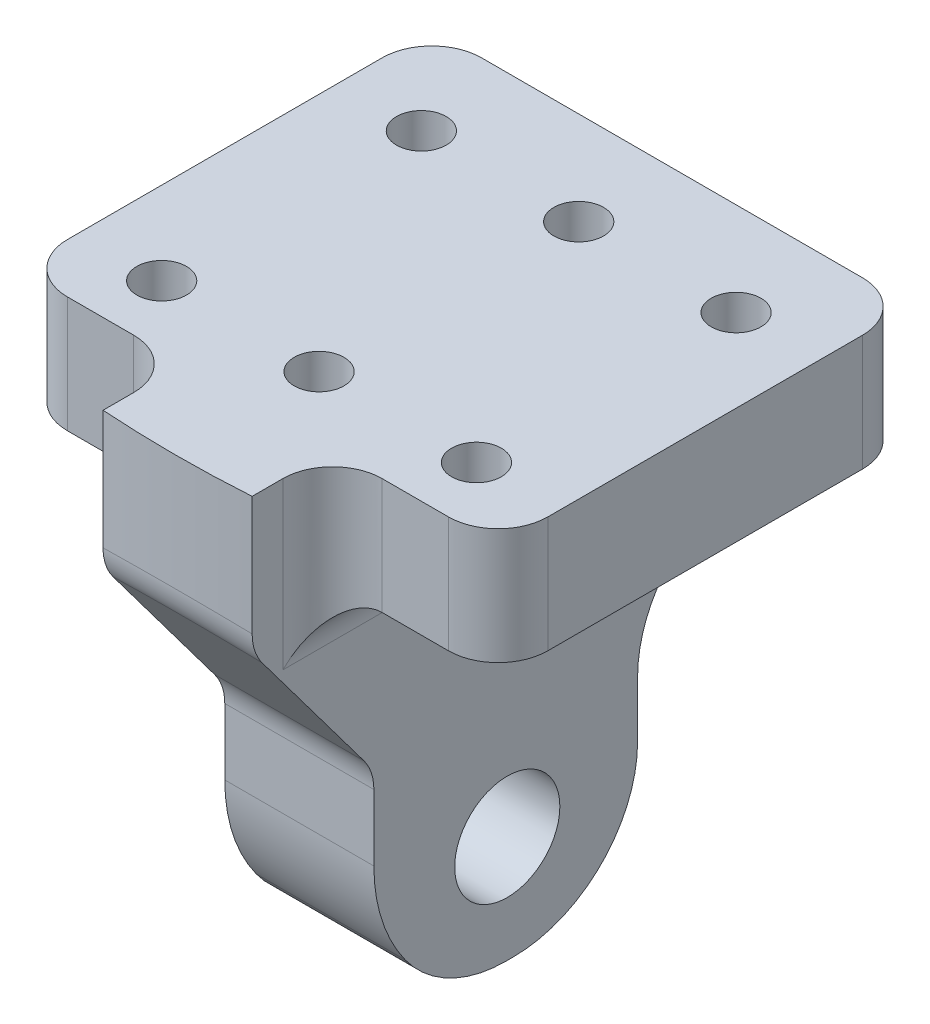
SolidWorks part; units mm, degrees
material "Custom Plastic"
ref_plane "Front Plane" through (0, 0, 0) normal (0, 0, 1) x (1, 0, 0)
ref_plane "Top Plane" through (0, 0, 0) normal (0, 1, 0) x (1, 0, 0)
ref_plane "Right Plane" through (0, 0, 0) normal (1, 0, 0) x (0, 0, -1)
sketch "Sketch1" plane through (0, 0, 0) normal (0, 1, 0) x (1, 0, 0)
  line L0 (0, 0) -> (0, 15.5524)
  line L2 (4.5, 0.1524) -> (4.5, 30)
  line L3 (4.5, 30) -> (-4.5, 30)
  line L4 (-4.5, 30) -> (-4.5, 0.1524)
  line L5 (0, 15.5524) -> (4.5, 15.5524)
  line L6 (0, 66.5) -> (0, 0) construction
  line L7 (-4.5, 0.1524) -> (4.5, 0.1524)
  circle A0 centre (0, 66.5) radius 66.5
  dimension "D3" = 133
  dimension "D1" = 9
  dimension "D2" = 30
  dimension "D4" = 15.4
extrude "Boss-Extrude1" add sketch "Sketch1" against normal blind 33 contours L0 L5 L2 L3 L4 | L5 L0 L2 | L7 A0 L0 | L0 A0 L7 | L7 L2 L3 L4 region at (-1.6878, 0, -0.0915) region at (1.6878, 0, -0.0915) region at (-0.7823, 0, -17.5877) region at (2.25, 0, -7.8524)
sketch "Sketch2" plane through (4.5, 0, 0) normal (1, 0, 0) x (0, 0, -1)
  line L0 (15.5524, 0) -> (15.5524, -33)
  line L1 (0.1524, -33) -> (30, -33) construction
  line L2 (15.5524, 0) -> (15.5524, -25.5)
  line L3 (0, 0) -> (0, -3)
  line L4 (0, 0) -> (0, -33) construction
  line L7 (0.1524, -33) -> (30, -33) construction
  line L8 (0, -3) -> (0, -33)
  line L9 (0, -33) -> (7.5, -33)
  line L10 (7.5, -33) -> (7.5, -18)
  line L15 (7.5, -18) -> (0, -18)
  line L16 (7.5, -18) -> (0, -8)
  circle A0 centre (15.5524, -25.5) radius 3.175
  line M4 (0.1524, -33) -> (30, -33)
  line M12 (0.1524, 0) -> (0.1524, -33)
  dimension "D2" = 6.35
  dimension "D1" = 7.5
  dimension "D3" = 15
  dimension "D4" = 7.5
  dimension "D5" = 10
extrude "Cut-Extrude1" cut sketch "Sketch2" against normal blind 20 contours L2 A0 L0 | L0 A0 L2 region at (4.5, -25.5, -16.8999) region at (4.5, -25.5, -14.2049)
extrude "Cut-Extrude2" cut sketch "Sketch2<4>" against normal blind 20 contours L10 L15 M12 M4 | L15 L8 L9 M12 | L15 L16 M12 | L16 L8 L15 M12 region at (4.5, -25.5, -3.8262) region at (4.5, -25.5, -0.0762) region at (4.5, -14.7344, -2.6016) region at (4.5, -13.0506, -0.076)
sketch "Sketch2<4>" plane through (4.5, 0, 0) normal (1, 0, 0) x (0, 0, -1) same geometry as "Sketch2"
fillet "Fillet1" radius 10 1 edges at (0, -33, -7.5)
sketch "Sketch3" plane through (0, 0, 0) normal (0, 1, 0) x (1, 0, 0)
  line L0 (4.5, 5.0023) -> (4.5, 12.3823)
  line L1 (-4.5, 30) -> (4.5, 30)
  line L2 (-4.5, 30) -> (-4.5, 5.0023)
  line L3 (-4.5, 5.0023) -> (4.5, 5.0023)
  line L4 (4.5, 30) -> (4.5, 5.0023)
  line L5 (4.5, 12.3823) -> (-4.5, 12.3823)
  line L6 (0, 18.7323) -> (0, 30)
  line L7 (-4.5, 12.3823) -> (4.5, 12.3823)
  line L8 (-4.5, 12.3823) -> (-4.5, 18.7323)
  line L9 (-4.5, 18.7323) -> (4.5, 18.7323)
  line L10 (4.5, 12.3823) -> (4.5, 18.7323)
  line L11 (0, 5.0023) -> (0, 12.3823)
  line L12 (0, 5.0023) -> (0, 8.6923)
  line L13 (0, 8.6923) -> (-4.5, 8.6923)
  line L14 (-4.5, 8.6923) -> (4.5, 8.6923)
  line L15 (-4.5, 5.0023) -> (-4.5, 0.1524)
  line L16 (-4.5, 0.1524) -> (4.5, 0.1524)
  line L17 (-9.5, 30) -> (-9.5, 5.0023) construction
  line L18 (4.5, 30) -> (14.5, 30)
  line L19 (4.5, 30) -> (4.5, 5.0023)
  line L20 (4.5, 5.0023) -> (14.5, 5.0023)
  line L21 (14.5, 30) -> (14.5, 5.0023)
  line L22 (-4.5, 5.0023) -> (-14.5, 5.0023)
  line L23 (-4.5, 5.0023) -> (-4.5, 30)
  line L24 (-4.5, 30) -> (-14.5, 30)
  line L25 (-14.5, 5.0023) -> (-14.5, 30)
  line L26 (9.5, 30) -> (9.5, 5.0023) construction
  line L27 (14.5, 24.3661) -> (-14.5, 24.3661) construction
  line L28 (14.5, 8.6923) -> (-14.5, 8.6923) construction
  circle A0 centre (0, 24.3661) radius 1.5
  circle A1 centre (0, 8.6923) radius 1.5
  circle A2 centre (-9.5, 24.3661) radius 1.5
  circle A3 centre (-9.5, 8.6923) radius 1.5
  circle A4 centre (9.5, 8.6923) radius 1.5
  circle A5 centre (9.5, 24.3661) radius 1.5
  point P13 (0, 24.3661)
  point P36 (0, 24.3661)
  point P39 (0, 8.6923)
  line M11 (-4.5, 30) -> (-4.5, 0.1524)
  line M13 (4.5, 0.1524) -> (4.5, 30)
  dimension "D3" = 3
  dimension "D1" = 12.2298
  dimension "D2" = 6.35
  dimension "D4" = 15.6739
  dimension "D5" = 3.69
  dimension "D6" = 4.5
  dimension "D7" = 10
extrude "Cut-Extrude3" cut sketch "Sketch3" against normal blind 7 contours A0
extrude "Cut-Extrude4" cut sketch "Sketch3<3>" against normal blind 7 contours A1
sketch "Sketch3<3>" plane through (0, 0, 0) normal (0, 1, 0) x (1, 0, 0) same geometry as "Sketch3"
extrude "Boss-Extrude2" add sketch "Sketch3<4>" against normal blind 10 contours L25 L22 L2 L24 A3 A2 M11 | L21 L18 L4 L20 A5 A4 M13 | A2 | A5 | A3 | A4 region at (9.5, 0, -17.5594) region at (-9.5, 0, -17.5594) region at (-9.5, 0, -24.3661) region at (-9.5, 0, -8.6923) region at (9.5, 0, -8.6923) region at (9.5, 0, -24.3661)
sketch "Sketch3<4>" plane through (0, 0, 0) normal (0, 1, 0) x (1, 0, 0) same geometry as "Sketch3"
extrude "Cut-Extrude5" cut sketch "Sketch3<5>" against normal blind 8 contours A3 | A4 | A5 | A2 region at (-9.5, 0, -8.6923) region at (9.5, 0, -8.6923) region at (9.5, 0, -24.3661)
sketch "Sketch3<5>" plane through (0, 0, 0) normal (0, 1, 0) x (1, 0, 0) same geometry as "Sketch3"
fillet "Fillet9" radius 3 2 edges at (0, -18, -7.5) (0, -8, 0)
sketch "Sketch20" plane through (0, 0, -5.0023) normal (0, 0, 1) x (1, 0, 0)
  line L0 (-14.5, -7) -> (14.5, -7)
  line L1 (-14.5, 0) -> (14.5, 0)
  line L2 (-14.5, 0) -> (-14.5, -10)
  line L3 (-14.5, -10) -> (14.5, -10)
  line L4 (14.5, 0) -> (14.5, -10)
  line L5 (-4.5, 0) -> (4.5, 0)
  line L6 (-4.5, 0) -> (-4.5, -10)
  line L7 (-4.5, -10) -> (4.5, -10)
  line L8 (4.5, 0) -> (4.5, -10)
  line L10 (-4.5, -10) -> (-4.5, 0) construction
  line M8 (-14.5, 0) -> (-14.5, -10)
  line M9 (-14.5, -10) -> (-4.5, -10)
  dimension "D1" = 3
extrude "Cut-Extrude6" cut sketch "Sketch20" against normal blind 25 contours M9 M8 | L3 L4 region at (-9.5, -8.5, -5.0023) region at (9.5, -8.5, -5.0023)
fillet "Fillet10" radius 3 2 edges at (4.5, -3.5, -5.0023) (-4.5, -3.5, -5.0023)
fillet "Fillet11" radius 10 1 edges at (0, -33, -30)
fillet "Fillet12" radius 3 4 edges at (14.5, -3.5, -30) (14.5, -3.5, -5.0023) (-14.5, -3.5, -30) (-14.5, -3.5, -5.0023)
fillet "Fillet13" radius 3 2 edges at (4.5, -7, -16.0011) (-4.5, -7, -16.0011)
sketch "Sketch21" plane through (0, 0, 0) normal (1, 0, 0) x (0, 0, -1)
  line L0 (30, -10) -> (23.4193, -18.5117)
  line L1 (23.4193, -18.5117) -> (23.4193, -32.3972)
  line L2 (23.4193, -32.3972) -> (31.1939, -32.3972)
  line L3 (31.1939, -32.3972) -> (31.1939, -10)
  line L4 (31.1939, -10) -> (30, -10)
  line L5 (7.7761, -31.9648) -> (23.4193, -31.9648)
  line L6 (23.4193, -31.9648) -> (23.4193, -35.3866)
  line L7 (23.4193, -35.3866) -> (7.4889, -35.3866)
  line L8 (7.4889, -35.3866) -> (7.7761, -31.9648)
  arc A0 (20, -33) -> (30, -23) centre (20, -23) ccw construction
extrude "Cut-Extrude7" cut sketch "Sketch21" against normal mid plane 10 contours L3 L4 L0 L1 L2 | L8 L7 L6 L1 L5 region at (0, -22.8012, -27.6312) region at (0, -33.6809, -15.5257)
fillet "Fillet17" radius 7.5 1 edges at (0, -31.9648, -23.4193)
fillet "Fillet18" radius 7.5 1 edges at (0, -31.9648, -13.0691)
fillet "Fillet19" radius 7.5 2 edges at (0, -10, -30) (0, -18.5117, -23.4193)
